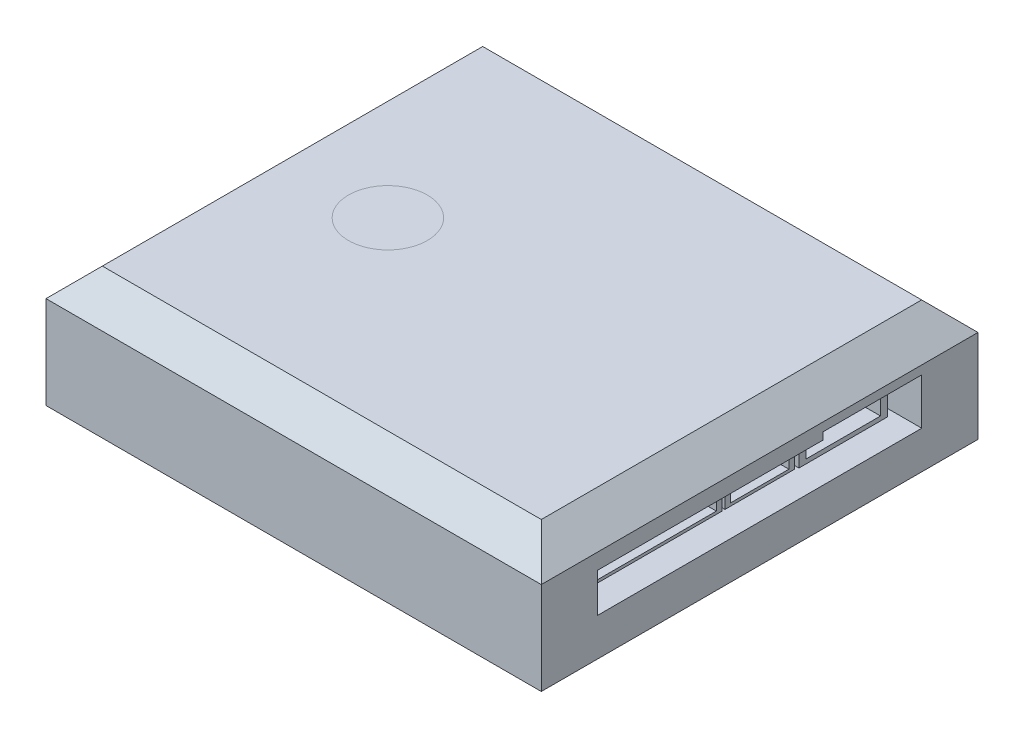
SolidWorks part; units mm, degrees
ref_plane "Front" through (0, 0, 0) normal (0, 0, 1) x (1, 0, 0)
ref_plane "Top" through (0, 0, 0) normal (0, 1, 0) x (1, 0, 0)
ref_plane "Right" through (0, 0, 0) normal (1, 0, 0) x (0, 0, -1)
sketch "Sketch1" plane through (0, 0, 0) normal (0, 1, 0) x (1, 0, 0)
  line L1 (-21.975, -19.375) -> (21.975, -19.375)
  line L2 (-21.975, -19.375) -> (-21.975, 19.375)
  line L3 (-21.975, 19.375) -> (21.975, 19.375)
  line L4 (21.975, -19.375) -> (21.975, 19.375)
  line L5 (-21.975, -19.375) -> (21.975, 19.375) construction
  line L6 (-21.975, 19.375) -> (21.975, -19.375) construction
  point P0 (0, 0)
  dimension "D1" = 43.95
  dimension "D2" = 38.75
extrude "Boss-Extrude1" add sketch "Sketch1" along normal blind 12.4968
chamfer "Chamfer1" distance 2.5 angle 45 4 edges at (0, 12.4968, 19.375) (-21.975, 12.4968, 0) (0, 12.4968, -19.375) (21.975, 12.4968, 0)
chamfer "Chamfer2" distance 1.778 angle 45 4 edges at (0, 0, -19.375) (-21.975, 0, 0) (0, 0, 19.375) (21.975, 0, 0)
sketch "Sketch2" plane through (21.975, 0, 0) normal (1, 0, 0) x (0, 0, -1)
  line L0 (19.375, 9.9968) -> (-19.375, 9.9968) construction
  line L1 (-14.3828, 8.5998) -> (14.3827, 8.5998)
  line L2 (-14.3828, 8.5998) -> (-14.3828, 5.1327)
  line L3 (-14.3828, 5.1327) -> (14.3827, 5.1327)
  line L4 (14.3827, 8.5998) -> (14.3827, 5.1327)
  line L5 (-14.3828, 8.5998) -> (14.3827, 5.1327) construction
  line L6 (-14.3828, 5.1327) -> (14.3827, 8.5998) construction
  line L7 (5.6197, 8.5998) -> (14.3827, 8.5998)
  line L8 (5.6197, 8.5998) -> (5.6197, 9.2348)
  line L9 (5.6197, 9.2348) -> (14.3827, 9.2348)
  line L10 (14.3827, 8.5998) -> (14.3827, 9.2348)
  point P0 (0, 6.8663)
  point P5 (14.3827, 8.9173)
  point P11 (14.3827, 6.8663)
  dimension "D1" = 28.7655
  dimension "D2" = 3.4671
  dimension "D3" = 4.1021
  dimension "D4" = 8.763
  dimension "D5" = 0.762
extrude "Cut-Extrude1" cut sketch "Sketch2" against normal blind 6.9342 contours L4 L1 L2 L3 | L1 L10 L9 L8 region at (21.975, 6.8663, 0) region at (21.975, 8.9173, -10.0012)
sketch "Sketch3" plane through (15.0408, 0, 0) normal (1, 0, 0) x (0, 0, -1)
  line L0 (-14.3828, 8.5998) -> (-14.3828, 5.1327) construction
  line L1 (-13.6208, 8.3712) -> (-1.0732, 8.3712)
  line L2 (-13.6208, 8.3712) -> (-13.6208, 5.3613)
  line L3 (-13.6208, 5.3613) -> (-1.0732, 5.3613)
  line L4 (-1.0732, 8.3712) -> (-1.0732, 5.3613)
  line L5 (5.6197, 8.5998) -> (5.6197, 9.2348) construction
  line L6 (5.7467, 9.1078) -> (13.6207, 9.1078)
  line L7 (5.7467, 9.1078) -> (5.7467, 5.2597)
  line L8 (5.7467, 5.2597) -> (13.6207, 5.2597)
  line L9 (13.6207, 9.1078) -> (13.6207, 5.2597)
  line L10 (14.3827, 9.2348) -> (14.3827, 5.1327) construction
  line L11 (5.6197, 9.2348) -> (14.3827, 9.2348) construction
  line L12 (-14.3828, 5.1327) -> (14.3827, 5.1327) construction
  line L13 (-7.347, 8.1172) -> (-7.347, 5.6153) construction
  line L14 (-0.8192, 8.3712) -> (5.3657, 8.3712)
  line L15 (-0.8192, 8.3712) -> (-0.8192, 5.3613)
  line L16 (-0.8192, 5.3613) -> (5.3657, 5.3613)
  line L17 (5.3657, 8.3712) -> (5.3657, 5.3613)
  line L18 (-13.1128, 8.1172) -> (-1.5812, 8.1172)
  line L19 (-13.1128, 8.1172) -> (-13.1128, 7.6092)
  line L20 (-13.1128, 5.6153) -> (-1.5812, 5.6153)
  line L21 (-1.5812, 8.1172) -> (-1.5812, 7.6092)
  line L22 (-13.1128, 7.1012) -> (-13.3668, 7.1012)
  line L23 (-1.5812, 7.1012) -> (-1.5812, 5.6153)
  line L24 (-13.1128, 7.6092) -> (-13.3668, 7.6092)
  line L25 (-13.3668, 7.1012) -> (-13.3668, 7.6092)
  line L26 (-1.3272, 7.1012) -> (-1.3272, 7.6092)
  line L27 (-1.5812, 7.6092) -> (-1.3272, 7.6092)
  line L28 (2.2733, 8.1172) -> (2.2733, 5.6153) construction
  line L29 (-1.5812, 7.1012) -> (-1.3272, 7.1012)
  line L30 (-13.1128, 7.1012) -> (-13.1128, 5.6153)
  line L31 (-0.3112, 8.1172) -> (4.8577, 8.1172)
  line L32 (-0.3112, 8.1172) -> (-0.3112, 7.6092)
  line L33 (-0.3112, 5.6153) -> (4.8577, 5.6153)
  line L34 (4.8577, 8.1172) -> (4.8577, 7.6092)
  line L35 (-0.3112, 7.1012) -> (-0.5652, 7.1012)
  line L36 (4.8577, 7.1012) -> (4.8577, 5.6153)
  line L37 (-0.3112, 7.6092) -> (-0.5652, 7.6092)
  line L38 (-0.5652, 7.1012) -> (-0.5652, 7.6092)
  line L39 (5.1117, 7.1012) -> (5.1117, 7.6092)
  line L40 (4.8577, 7.6092) -> (5.1117, 7.6092)
  line L41 (9.6837, 8.7268) -> (9.6837, 5.6407) construction
  line L42 (4.8577, 7.1012) -> (5.1117, 7.1012)
  line L43 (-0.3112, 7.1012) -> (-0.3112, 5.6153)
  line L44 (6.3817, 8.7268) -> (12.9857, 8.7268)
  line L45 (6.3817, 8.7268) -> (6.3817, 8.2188)
  line L46 (6.3817, 5.6407) -> (12.9857, 5.6407)
  line L47 (12.9857, 8.7268) -> (12.9857, 8.2188)
  line L48 (6.3817, 7.4568) -> (6.0007, 7.4568)
  line L49 (12.9857, 7.4568) -> (12.9857, 5.6407)
  line L50 (6.3817, 8.2188) -> (6.0007, 8.2188)
  line L51 (6.0007, 7.4568) -> (6.0007, 8.2188)
  line L52 (13.3667, 7.4568) -> (13.3667, 8.2188)
  line L53 (12.9857, 8.2188) -> (13.3667, 8.2188)
  line L55 (12.9857, 7.4568) -> (13.3667, 7.4568)
  line L56 (6.3817, 7.4568) -> (6.3817, 5.6407)
  point P4 (-13.6208, 6.8663)
  point P7 (-14.3828, 6.8663)
  point P14 (5.6197, 8.9173)
  dimension "D1" = 0.762
  dimension "D2" = 12.5476
  dimension "D3" = 3.0099
  dimension "D4" = 0.127
  dimension "D5" = 0.762
  dimension "D6" = 0.127
  dimension "D7" = 0.127
  dimension "D8" = 0.254
  dimension "D9" = 0.254
  dimension "D10" = 0.254
  dimension "D11" = 0.254
  dimension "D12" = 0.508
  dimension "D13" = 0.508
  dimension "D14" = 0.508
  dimension "D15" = 0.508
  dimension "D16" = 0.254
  dimension "D17" = 0.508
  dimension "D18" = 0.508
  dimension "D19" = 0.254
  dimension "D20" = 0.381
  dimension "D21" = 0.381
  dimension "D22" = 0.635
  dimension "D23" = 0.635
  dimension "D24" = 0.381
  dimension "D25" = 0.762
  dimension "D26" = 0.508
extrude "Boss-Extrude2" add sketch "Sketch3" along normal offset from surface (4.6736 mm away) 2.2606 contours L22 L30 L20 L23 L29 L26 L27 L21 L18 L19 L24 L25 | L35 L43 L33 L36 L42 L39 L40 L34 L31 L32 L37 L38 | L48 L56 L46 L49 L55 L52 L53 L47 L44 L45 L50 L51 | L4 L1 L2 L3 L30 L22 L25 L24 L19 L18 L21 L27 L26 L29 L23 L20 | L17 L14 L15 L16 L43 L35 L38 L37 L32 L31 L34 L40 L39 L42 L36 L33 | L9 L6 L7 L8 L56 L48 L51 L50 L45 L44 L47 L53 L52 L55 L49 L46 region at (15.0408, 8.2422, 7.347) region at (15.0408, 9.0202, -9.6837) region at (15.0408, 8.3024, -2.2733) region at (15.0408, 6.8706, 7.347) region at (15.0408, 6.8758, -2.2733) region at (15.0408, 7.2019, -9.6837) up to face at (21.975, 5.8874, 0)
extrude "Cut-Extrude3" cut sketch "Sketch3<4>" along normal up to surface (4.6736 mm away) from offset 1.27 contours L22 L30 L20 L23 L29 L26 L27 L21 L18 L19 L24 L25 | L35 L43 L33 L36 L42 L39 L40 L34 L31 L32 L37 L38 | L48 L56 L46 L49 L55 L52 L53 L47 L44 L45 L50 L51 region at (15.0408, 6.8706, 7.347) region at (15.0408, 6.8758, -2.2733) region at (15.0408, 7.2019, -9.6837) up to face at (19.7144, 6.8663, 7.347)
sketch "Sketch3<4>" plane through (15.0408, 0, 0) normal (1, 0, 0) x (0, 0, -1) same geometry as "Sketch3"
sketch "Sketch4" plane through (16.3108, 0, 0) normal (1, 0, 0) x (0, 0, -1)
  line L0 (-13.3668, 7.3552) -> (-1.3272, 7.3552) construction
  line L1 (-13.3668, 7.6092) -> (-13.3668, 7.1012) construction
  line L2 (-1.3272, 7.6092) -> (-1.3272, 7.1012) construction
  line L3 (-0.5652, 7.3552) -> (5.1117, 7.3552) construction
  line L4 (-0.5652, 7.6092) -> (-0.5652, 7.1012) construction
  line L5 (5.1117, 7.6092) -> (5.1117, 7.1012) construction
  line L6 (6.0007, 7.8378) -> (13.3667, 7.8378) construction
  line L7 (6.0007, 7.4568) -> (6.0007, 8.2188) construction
  line L8 (13.3667, 7.4568) -> (13.3667, 8.2188) construction
  circle A0 centre (-12.6299, 7.3552) radius 0.1905
  circle A1 centre (-11.4615, 7.3552) radius 0.1905
  circle A2 centre (-10.2931, 7.3552) radius 0.1905
  circle A3 centre (-9.1247, 7.3552) radius 0.1905
  circle A4 centre (-7.9563, 7.3552) radius 0.1905
  circle A5 centre (-6.7879, 7.3552) radius 0.1905
  circle A6 centre (-5.6195, 7.3552) radius 0.1905
  circle A7 centre (-4.4511, 7.3552) radius 0.1905
  circle A8 centre (-3.2827, 7.3552) radius 0.1905
  circle A9 centre (-2.1143, 7.3552) radius 0.1905
  circle A10 centre (0.343, 7.3552) radius 0.1905
  circle A11 centre (2.248, 7.3552) radius 0.1905
  circle A12 centre (4.153, 7.3552) radius 0.1905
  circle A13 centre (7.146, 7.8378) radius 0.254
  circle A14 centre (9.686, 7.8378) radius 0.254
  circle A15 centre (12.226, 7.8378) radius 0.254
  point P46 (7.146, 7.8378)
  point P51 (0.2679, 7.3552)
  point P52 (0.343, 7.3552)
  dimension "D1" = 0.381
  dimension "D3" = 1.1684
  dimension "D4" = 0.381
  dimension "D6" = 0.508
  dimension "D8" = 1.905
  dimension "D2" = 10
  dimension "D5" = 3
  dimension "D7" = 3
extrude "Pins" add sketch "Sketch4" along normal blind 3.0226
sketch "Sketch5" plane through (0, 12.4968, 0) normal (0, 1, 0) x (1, 0, 0)
  line L0 (0, 0) -> (-17.7525, -0.8354) construction
  circle A0 centre (-10.5173, -0.4949) radius 3.5
  point P2 (-10.5173, -0.4949)
  dimension "D1" = 7
split line "LED"
sketch "Sketch6" plane through (0, 0, -19.375) normal (0, 0, -1) x (-1, 0, 0)
  line L0 (62.7526, 70.2944) -> (222.4815, 70.2944) construction
  line L1 (4.577, 8.7842) -> (4.577, 6.3643) construction
  line L2 (2.595, 7.7857) -> (2.341, 7.7857)
  line L3 (8.3371, 7.7857) -> (8.3371, 6.3643)
  line L4 (3.2162, 5.8563) -> (5.5914, 5.8563)
  line L5 (2.595, 8.2937) -> (2.341, 8.2937)
  line L6 (2.595, 8.7842) -> (6.5591, 8.7842)
  line L7 (2.595, 8.7842) -> (2.595, 8.2937)
  line L8 (2.341, 7.7857) -> (2.341, 8.2937)
  line L9 (10.9231, 8.7842) -> (10.9231, 6.3643) construction
  line L11 (5.5914, 5.8563) -> (14.7792, 5.8563)
  line L12 (1.579, 9.2922) -> (14.7792, 9.2922)
  line L13 (1.579, 9.2922) -> (1.579, 5.8563)
  line L14 (1.579, 5.8563) -> (3.2162, 5.8563)
  line L15 (14.7792, 9.2922) -> (14.7792, 5.8563)
  line L16 (2.595, 6.3643) -> (6.5591, 6.3643)
  line L17 (6.5591, 8.7842) -> (6.5591, 8.2937)
  line L18 (8.3371, 8.7842) -> (13.5092, 8.7842)
  line L19 (8.3371, 8.7842) -> (8.3371, 8.2937)
  line L20 (2.087, 9.0382) -> (7.0671, 9.0382)
  line L21 (2.087, 9.0382) -> (2.087, 6.1103)
  line L22 (2.087, 6.1103) -> (7.0671, 6.1103)
  line L23 (7.0671, 9.0382) -> (7.0671, 6.1103)
  line L24 (7.8291, 9.0382) -> (14.0172, 9.0382)
  line L25 (7.8291, 9.0382) -> (7.8291, 6.1103)
  line L26 (7.8291, 6.1103) -> (14.0172, 6.1103)
  line L27 (14.0172, 9.0382) -> (14.0172, 6.1103)
  line L28 (8.3371, 6.3643) -> (13.5092, 6.3643)
  line L29 (13.5092, 8.7842) -> (13.5092, 8.2937)
  line L30 (8.3371, 7.7857) -> (8.0831, 7.7857)
  line L31 (13.5092, 7.7857) -> (13.5092, 6.3643)
  line L32 (8.3371, 8.2937) -> (8.0831, 8.2937)
  line L33 (8.0831, 7.7857) -> (8.0831, 8.2937)
  line L34 (6.8131, 7.7857) -> (6.8131, 8.2937)
  line L35 (6.5591, 8.2937) -> (6.8131, 8.2937)
  line L37 (6.5591, 7.7857) -> (6.8131, 7.7857)
  line L38 (13.7632, 7.7857) -> (13.7632, 8.2937)
  line L39 (13.5092, 8.2937) -> (13.7632, 8.2937)
  line L41 (13.5092, 7.7857) -> (13.7632, 7.7857)
  line L42 (2.595, 7.7857) -> (2.595, 6.3643)
  line L43 (6.5591, 7.7857) -> (6.5591, 6.3643)
  point P10 (2.087, 7.5743)
  point P30 (14.0172, 7.5743)
  point P31 (14.7792, 7.5743)
  dimension "D1" = 0.254
  dimension "D2" = 0.254
  dimension "D3" = 0.254
  dimension "D4" = 0.254
  dimension "D5" = 0.762
  dimension "D6" = 0.762
  dimension "D7" = 0.508
  dimension "D8" = 0.254
  dimension "D9" = 0.254
  dimension "D10" = 0.508
  dimension "D11" = 0.508
  dimension "D12" = 0.508
  dimension "D13" = 0.508
  dimension "D14" = 0.254
  dimension "D15" = 0.508
  dimension "D16" = 0.254
extrude "Cut-Extrude4" cut sketch "Sketch6" against normal blind 7.366 contours L15 L12 L13 L14 L4 L11 L20 L23 L22 L21 L24 L27 L26 L25 | L43 L37 L34 L35 L17 L6 L7 L5 L8 L2 L42 L16 | L31 L41 L38 L39 L29 L18 L19 L32 L33 L30 L3 L28 | L23 L20 L21 L22 L37 L43 L16 L42 L2 L8 L5 L7 L6 L17 L35 L34 | L27 L24 L25 L26 L41 L31 L28 L3 L30 L33 L32 L19 L18 L29 L39 L38 region at (-4.577, 7.5865, -19.375) region at (-10.9231, 7.5837, -19.375) region at (-2.3976, 5.9927, -19.375) region at (-4.577, 8.9805, -19.375) region at (-10.9231, 8.9698, -19.375)
extrude "Boss-Extrude6" add sketch "Sketch6<7>" against normal blind 7.366 from offset 2.286 contours L23 L20 L21 L22 L37 L43 L16 L42 L2 L8 L5 L7 L6 L17 L35 L34 | L27 L24 L25 L26 L41 L31 L28 L3 L30 L33 L32 L19 L18 L29 L39 L38 region at (-4.577, 8.9805, -19.375) region at (-10.9231, 8.9698, -19.375) offset against normal yes
sketch "Sketch6<7>" plane through (0, 0, -19.375) normal (0, 0, -1) x (-1, 0, 0) same geometry as "Sketch6"
extrude "Boss-Extrude7" add sketch "Sketch6<8>" along normal blind 1.27 from offset 5.08 contours L43 L37 L34 L35 L17 L6 L7 L5 L8 L2 L42 L16 | L31 L41 L38 L39 L29 L18 L19 L32 L33 L30 L3 L28 region at (-4.577, 7.5865, -19.375) region at (-10.9231, 7.5837, -19.375) offset against normal yes
sketch "Sketch6<8>" plane through (0, 0, -19.375) normal (0, 0, -1) x (-1, 0, 0) same geometry as "Sketch6"
sketch "Sketch7" plane through (0, 0, -15.565) normal (0, 0, -1) x (-1, 0, 0)
  line L0 (2.341, 8.0397) -> (6.8131, 8.0397) construction
  line L1 (2.341, 7.7857) -> (2.341, 8.2937) construction
  line L2 (6.8131, 7.7857) -> (6.8131, 8.2937) construction
  line L3 (8.0831, 8.0397) -> (13.7632, 8.0397) construction
  line L4 (8.0831, 7.7857) -> (8.0831, 8.2937) construction
  line L5 (13.7632, 7.7857) -> (13.7632, 8.2937) construction
  circle A0 centre (3.2393, 8.0397) radius 0.1905
  circle A1 centre (8.9588, 8.0397) radius 0.1905
  circle A2 centre (4.5093, 8.0397) radius 0.1905
  circle A3 centre (5.7793, 8.0397) radius 0.1905
  circle A4 centre (10.2288, 8.0397) radius 0.1905
  circle A5 centre (11.4988, 8.0397) radius 0.1905
  circle A6 centre (12.7688, 8.0397) radius 0.1905
  point P16 (8.995, 8.0397)
  point P17 (8.9588, 8.0397)
  dimension "D1" = 0.381
  dimension "D2" = 0.381
  dimension "D3" = 3
  dimension "D4" = 4
extrude "Boss-Extrude8" add sketch "Sketch7" along normal blind 1.524
sketch "Sketch8" plane through (-21.975, 0, 0) normal (-1, 0, 0) x (0, 0, 1)
  line L0 (494.9714, 1194.3432) -> (2000.69, 1194.3432) construction
  line L1 (-19.375, 0) -> (19.4341, 0)
  line L2 (-19.375, 0) -> (-19.375, 12.5052)
  line L3 (-19.375, 12.5052) -> (19.4341, 12.5052)
  line L4 (19.4341, 0) -> (19.4341, 12.5052)
  line L5 (-8.9037, 8.4372) -> (-8.9037, 5.9082) construction
  line L6 (-13.8236, 9.4532) -> (13.8738, 9.4532)
  line L7 (-13.8236, 9.4532) -> (-13.8236, 5.1462)
  line L8 (-13.8236, 5.1462) -> (13.8738, 5.1462)
  line L9 (13.8738, 9.4532) -> (13.8738, 5.1462)
  line L10 (-13.0616, 8.6912) -> (-4.7458, 8.6912)
  line L11 (-13.0616, 8.6912) -> (-13.0616, 5.6542)
  line L12 (-13.0616, 5.6542) -> (-4.7458, 5.6542)
  line L13 (-4.7458, 8.6912) -> (-4.7458, 5.6542)
  line L14 (-3.2218, 8.6912) -> (2.9406, 8.6912)
  line L15 (-3.2218, 8.6912) -> (-3.2218, 5.6542)
  line L16 (-3.2218, 5.6542) -> (2.9406, 5.6542)
  line L17 (2.9406, 8.6912) -> (2.9406, 5.6542)
  line L18 (4.4646, 8.6912) -> (13.1118, 8.6912)
  line L19 (4.4646, 8.6912) -> (4.4646, 5.6542)
  line L20 (4.4646, 5.6542) -> (13.1118, 5.6542)
  line L21 (13.1118, 8.6912) -> (13.1118, 5.6542)
  line L22 (-12.5536, 8.4372) -> (-5.2538, 8.4372)
  line L23 (-12.5536, 8.4372) -> (-12.5536, 7.9417)
  line L24 (-12.5536, 5.9082) -> (-5.2538, 5.9082)
  line L25 (-5.2538, 8.4372) -> (-5.2538, 7.9417)
  line L26 (-2.7138, 8.4372) -> (2.4326, 8.4372)
  line L27 (-2.7138, 8.4372) -> (-2.7138, 7.9417)
  line L28 (-2.7138, 5.9082) -> (2.4326, 5.9082)
  line L29 (2.4326, 8.4372) -> (2.4326, 7.9417)
  line L30 (4.9726, 8.4372) -> (12.6038, 8.4372)
  line L31 (4.9726, 8.4372) -> (4.9726, 7.9417)
  line L32 (4.9726, 5.9082) -> (12.6038, 5.9082)
  line L33 (12.6038, 8.4372) -> (12.6038, 7.9417)
  line L34 (-12.5536, 7.4337) -> (-12.8076, 7.4337)
  line L35 (-5.2538, 7.4337) -> (-5.2538, 5.9082)
  line L36 (-12.5536, 7.9417) -> (-12.8076, 7.9417)
  line L37 (-12.8076, 7.4337) -> (-12.8076, 7.9417)
  line L38 (-0.1406, 8.4372) -> (-0.1406, 5.9082) construction
  line L39 (8.7882, 8.4372) -> (8.7882, 5.9082) construction
  line L41 (-2.7138, 7.9417) -> (-2.9678, 7.9417)
  line L42 (2.4326, 7.4337) -> (2.4326, 5.9082)
  line L43 (-2.7138, 7.4337) -> (-2.9678, 7.4337)
  line L44 (-2.9678, 7.9417) -> (-2.9678, 7.4337)
  line L45 (-4.9998, 7.4337) -> (-4.9998, 7.9417)
  line L46 (4.9726, 7.4337) -> (4.7186, 7.4337)
  line L47 (12.6038, 7.4337) -> (12.6038, 5.9082)
  line L48 (4.9726, 7.9417) -> (4.7186, 7.9417)
  line L49 (4.7186, 7.4337) -> (4.7186, 7.9417)
  line L50 (-5.2538, 7.9417) -> (-4.9998, 7.9417)
  line L51 (-2.7138, 7.4337) -> (-2.7138, 5.9082)
  line L52 (-5.2538, 7.4337) -> (-4.9998, 7.4337)
  line L53 (2.6866, 7.9417) -> (2.6866, 7.4337)
  line L54 (2.4326, 7.4337) -> (2.6866, 7.4337)
  line L55 (4.9726, 7.4337) -> (4.9726, 5.9082)
  line L56 (2.4326, 7.9417) -> (2.6866, 7.9417)
  line L57 (12.8578, 7.4337) -> (12.8578, 7.9417)
  line L58 (12.6038, 7.9417) -> (12.8578, 7.9417)
  line L60 (12.6038, 7.4337) -> (12.8578, 7.4337)
  line L61 (-12.5536, 7.4337) -> (-12.5536, 5.9082)
  point P34 (-3.2218, 7.1727)
  dimension "D1" = 0.762
  dimension "D2" = 0.762
  dimension "D3" = 1.524
  dimension "D4" = 1.524
  dimension "D5" = 0.508
  dimension "D6" = 0.762
  dimension "D7" = 10.6019
  dimension "D8" = 6.1624
  dimension "D9" = 0.254
  dimension "D10" = 0.254
  dimension "D11" = 0.508
  dimension "D12" = 0.508
  dimension "D13" = 0.508
  dimension "D14" = 0.508
  dimension "D15" = 0.508
  dimension "D16" = 0.508
  dimension "D17" = 0.254
  dimension "D18" = 0.508
  dimension "D19" = 0.254
  dimension "D20" = 0.254
extrude "Cut-Extrude5" cut sketch "Sketch8" against normal offset from surface (7.1704 mm away) 0.0254 contours L9 L6 L7 L8 L10 L13 L12 L11 L14 L17 L16 L15 L18 L21 L20 L19 | L13 L10 L11 L12 L61 L34 L37 L36 L23 L22 L25 L50 L45 L52 L35 L24 | L34 L61 L24 L35 L52 L45 L50 L25 L22 L23 L36 L37 | L17 L14 L15 L16 L29 L56 L53 L54 L42 L28 L51 L43 L44 L41 L27 L26 | L56 L29 L26 L27 L41 L44 L43 L51 L28 L42 L54 L53 | L21 L18 L19 L20 L60 L47 L32 L55 L46 L49 L48 L31 L30 L33 L58 L57 | L47 L60 L57 L58 L33 L30 L31 L48 L49 L46 L55 L32 region at (-21.975, 9.1729, 0.0251) region at (-21.975, 8.6027, -8.9037) region at (-21.975, 8.6225, -0.1406) region at (-21.975, 8.5996, 8.7882) region at (-21.975, 7.1798, -8.9037) region at (-21.975, 7.1827, -0.1406) region at (-21.975, 7.1795, 8.7882) up to face at (-14.7792, 7.5743, -15.692)
extrude "Boss-Extrude9" add sketch "Sketch8<3>" against normal up to surface (7.1704 mm away) from offset 2.286 contours L13 L10 L11 L12 L61 L34 L37 L36 L23 L22 L25 L50 L45 L52 L35 L24 | L17 L14 L15 L16 L29 L56 L53 L54 L42 L28 L51 L43 L44 L41 L27 L26 | L21 L18 L19 L20 L60 L47 L32 L55 L46 L49 L48 L31 L30 L33 L58 L57 region at (-21.975, 8.6027, -8.9037) region at (-21.975, 8.6225, -0.1406) region at (-21.975, 8.5996, 8.7882) up to face at (-14.8046, 7.2997, 0.0251) offset against normal yes
sketch "Sketch8<3>" plane through (-21.975, 0, 0) normal (-1, 0, 0) x (0, 0, 1) same geometry as "Sketch8"
extrude "Boss-Extrude10" add sketch "Sketch8<5>" along normal blind 1.27 from offset 7.112 contours L34 L61 L24 L35 L52 L45 L50 L25 L22 L23 L36 L37 | L56 L29 L26 L27 L41 L44 L43 L51 L28 L42 L54 L53 | L47 L60 L57 L58 L33 L30 L31 L48 L49 L46 L55 L32 region at (-21.975, 7.1798, -8.9037) region at (-21.975, 7.1827, -0.1406) region at (-21.975, 7.1795, 8.7882) offset against normal yes
sketch "Sketch8<5>" plane through (-21.975, 0, 0) normal (-1, 0, 0) x (0, 0, 1) same geometry as "Sketch8"
sketch "Sketch9" plane through (-16.133, 0, 0) normal (-1, 0, 0) x (0, 0, 1)
  line L0 (-12.8076, 7.6877) -> (12.8578, 7.6877) construction
  line L1 (-12.8076, 7.4337) -> (-12.8076, 7.9417) construction
  line L2 (12.8578, 7.4337) -> (12.8578, 7.9417) construction
  circle A0 centre (-12.0997, 7.6877) radius 0.1905
  circle A1 centre (-2.0834, 7.6877) radius 0.1905
  circle A2 centre (5.583, 7.6877) radius 0.1905
  circle A3 centre (-10.8297, 7.6877) radius 0.1905
  circle A4 centre (-9.5597, 7.6877) radius 0.1905
  circle A5 centre (-8.2897, 7.6877) radius 0.1905
  circle A6 centre (-7.0197, 7.6877) radius 0.1905
  circle A7 centre (-5.7497, 7.6877) radius 0.1905
  circle A8 centre (6.853, 7.6877) radius 0.1905
  circle A9 centre (8.123, 7.6877) radius 0.1905
  circle A10 centre (9.393, 7.6877) radius 0.1905
  circle A11 centre (10.663, 7.6877) radius 0.1905
  circle A12 centre (11.933, 7.6877) radius 0.1905
  circle A13 centre (-0.8134, 7.6877) radius 0.1905
  circle A14 centre (0.4566, 7.6877) radius 0.1905
  circle A15 centre (1.7266, 7.6877) radius 0.1905
  point P34 (-2.0623, 7.6877)
  point P39 (-2.0834, 7.6877)
  dimension "D1" = 0.381
  dimension "D2" = 6
  dimension "D3" = 6
  dimension "D4" = 4
extrude "Boss-Extrude11" add sketch "Sketch9" along normal blind 3.302
